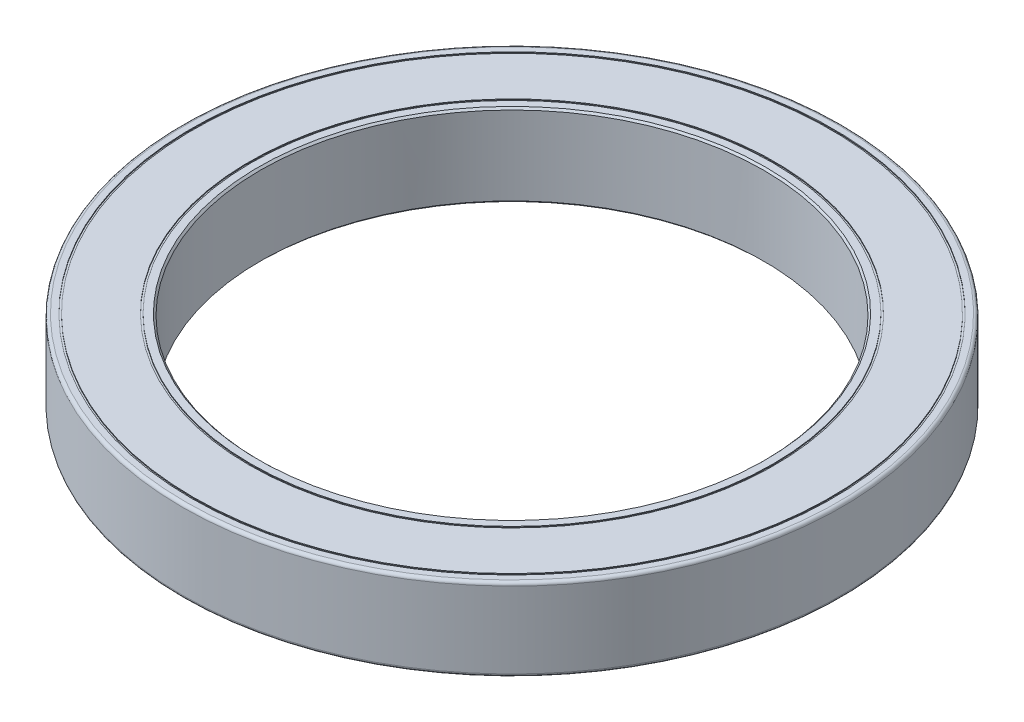
SolidWorks part; units mm, degrees
ref_plane "Front Plane" through (0, 0, 0) normal (0, 0, 1) x (1, 0, 0)
ref_plane "Top Plane" through (0, 0, 0) normal (0, 1, 0) x (1, 0, 0)
ref_plane "Right Plane" through (0, 0, 0) normal (1, 0, 0) x (0, 0, -1)
sketch "Sketch1" plane through (0, 0, 0) normal (0, 0, 1) x (1, 0, 0)
  line L0 (0, 0) -> (27.5, 0) construction
  line L1 (36, 0) -> (36, 9)
  line L3 (0, 4.5) -> (0, 0) construction
  line L4 (27.5, 0) -> (27.5, 9)
  line L5 (27.5, 0) -> (28.5, 0)
  line L6 (28.5, 0) -> (28.5, 0.1)
  line L7 (28.5, 0.1) -> (28.7, 0.1)
  line L8 (28.7, 0.1) -> (28.7, 0)
  line L9 (28.7, 0) -> (34.8, 0)
  line L10 (31.75, 0) -> (31.75, 4.5) construction
  line L11 (36, 4.5) -> (27.5, 4.5) construction
  line L12 (27.5, 4.5) -> (0, 4.5) construction
  line L13 (34.8, 0.1) -> (34.8, 0)
  line L14 (35, 0.1) -> (34.8, 0.1)
  line L15 (35, 0) -> (35, 0.1)
  line L16 (36, 0) -> (35, 0)
  line L17 (36, 9) -> (35, 9)
  line L18 (35, 9) -> (35, 8.9)
  line L19 (35, 8.9) -> (34.8, 8.9)
  line L20 (34.8, 8.9) -> (34.8, 9)
  line L21 (28.7, 9) -> (34.8, 9)
  line L22 (28.7, 8.9) -> (28.7, 9)
  line L23 (28.5, 8.9) -> (28.7, 8.9)
  line L24 (28.5, 9) -> (28.5, 8.9)
  line L25 (27.5, 9) -> (28.5, 9)
  dimension "D1" = 36
  dimension "D2" = 27.5
  dimension "D4" = 1
  dimension "D5" = 0.2
  dimension "D6" = 0.1
  dimension "D3" = 9
revolve "Revolve1" add sketch "Sketch1" angle 360 about L3
fillet "Fillet2" radius 0.344 2 edges at (0, 0, 36) (0, 9, 36)
chamfer "Chamfer2" distance 0.2 angle 45 2 edges at (0, 0, 27.5) (0, 9, 27.5)
equation "\"Ratio\"= 15"
equation "\"Hull Diameter\"= 3.5in"
equation "\"Fixed Ring Diameter\"= 76"
equation "\"Fixed Pin Diameter\"= 6"
equation "\"Output Ring Diameter\"= 40"
equation "\"Output Pin Diameter\"= 6"
equation "\"Disk Bearing Inner Diameter\"= 9"
equation "\"Disk Bearing Outer Diameter\"= 17"
equation "\"Disk Bearing Height\"= 5"
equation "\"Shaft Bearing Inner Diameter\"= 15"
equation "\"Shaft Bearing Outer Diameter\"= 21"
equation "\"Shaft Bearing Height\"= 4"
equation "\"Eccentricity\"= 1.5"
equation "\"Disk Height\"= 8"
equation "\"Disk Spacing\"= 5"
equation "\"Hull Height\"= 40"
equation "\"Shaft End Bearing Inner Diameter\"= 12"
equation "\"Shaft End Bearing Outer Diameter\"= 18"
equation "\"Shaft End Bearing Height\"= 4"
equation "\"Output Bearing Inner Diameter\"= 55"
equation "\"Output Bearing Outer Diameter\"= 72"
equation "\"Outer Bearing Height\"= 9"
equation "\"D3@Sketch1\"=\"Outer Bearing Height\""
equation "\"D2@Sketch1\"=\"Output Bearing Inner Diameter\"/2"
equation "\"D1@Sketch1\"=\"Output Bearing Outer Diameter\"/2"
